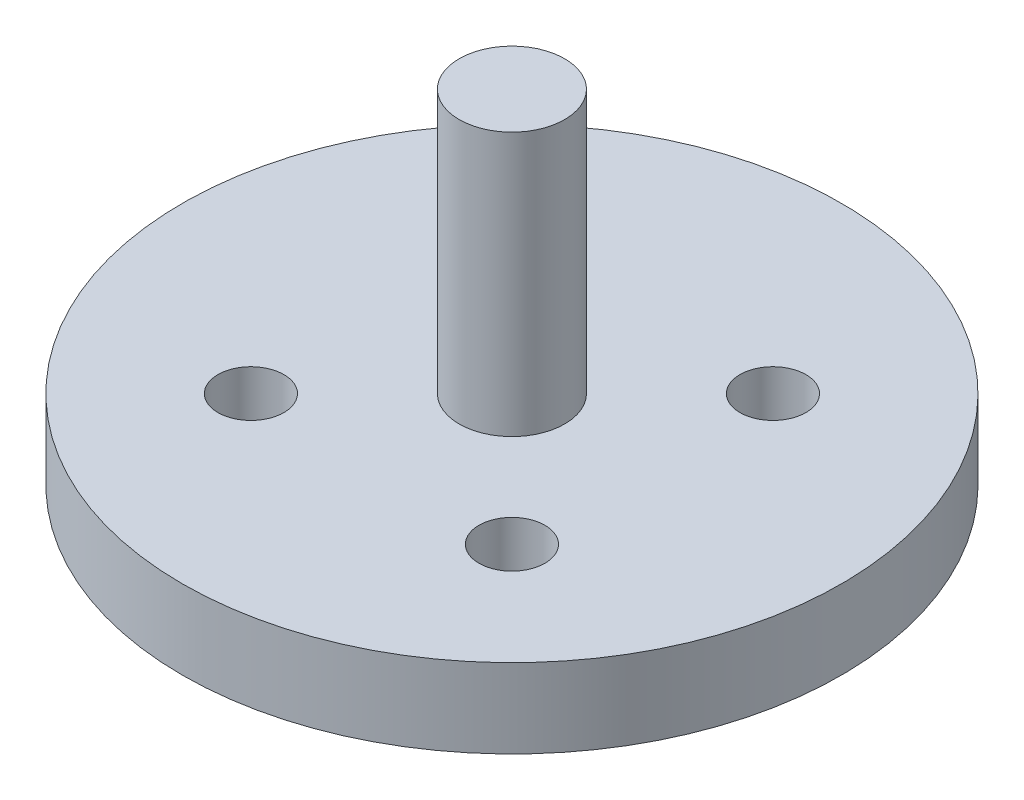
SolidWorks part; units mm, degrees
ref_plane "Alzado" through (0, 0, 0) normal (0, 0, 1) x (1, 0, 0)
ref_plane "Planta" through (0, 0, 0) normal (0, 1, 0) x (1, 0, 0)
ref_plane "Vista lateral" through (0, 0, 0) normal (1, 0, 0) x (0, 0, -1)
sketch "Croquis1" plane through (0, 0, 0) normal (0, 1, 0) x (1, 0, 0)
  line L0 (0, 0) -> (-6.6149, 6.6149) construction
  line L1 (-6.6149, 6.6149) -> (7.3418, -7.3418) construction
  line L2 (0, 0) -> (-6.786, -6.786) construction
  line L3 (-6.786, -6.786) -> (7.1299, 7.1299) construction
  circle A0 centre (0, 0) radius 12.5
  circle A1 centre (-4.9497, 4.9497) radius 1.25
  circle A6 centre (0, 0) radius 2
  circle A7 centre (4.9497, 4.9497) radius 1.25
  circle A8 centre (4.9497, -4.9497) radius 1.25
  circle A9 centre (-4.9497, -4.9497) radius 1.25
  point P14 (-1.6569, -4)
  point P23 (0, 0)
  dimension "D1" = 25
  dimension "D2" = 2.5
  dimension "D4" = 7
  dimension "D6" = 4
  dimension "D7" = 45
  dimension "D3" = 4
extrude "Saliente-Extruir1" add sketch "Croquis1" along normal blind 3 contours A0 A6 A1 | A6 region at (-12.1464, 0, 0) region at (0, 0, 0)
extrude "Saliente-Extruir2" add sketch "Croquis1<3>" along normal blind 10 from surface contours A6 starting at face at (-4.9497, 3, 6.1997)
sketch "Croquis1<3>" plane through (0, 0, 0) normal (0, 1, 0) x (1, 0, 0) same geometry as "Croquis1"
